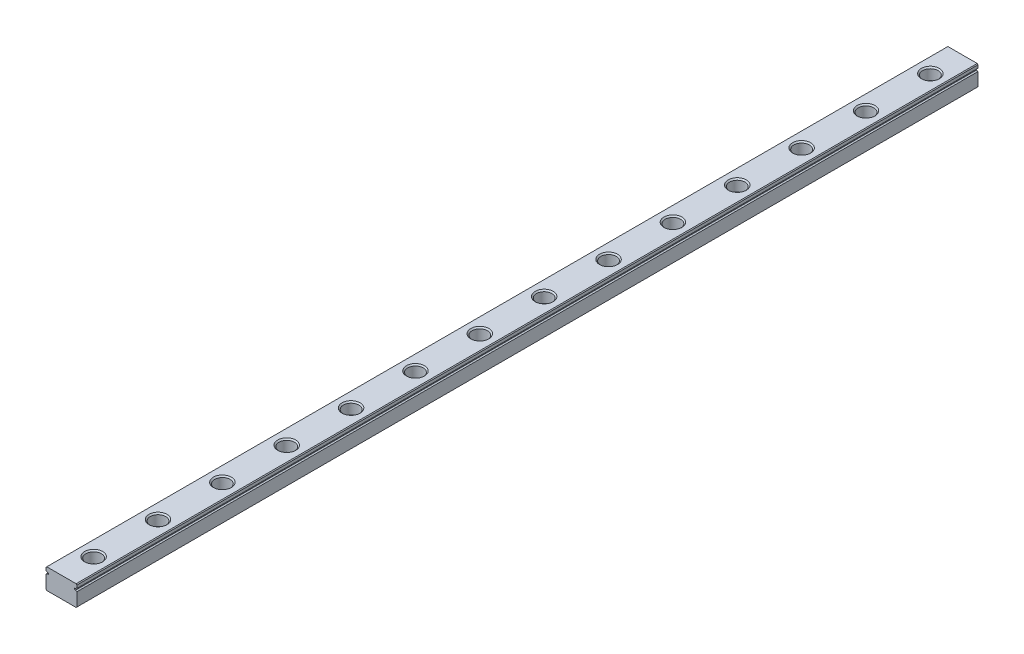
SolidWorks part; units mm, degrees
material "AISI 1045 鋼，冷拉"
ref_plane "Front Plane" through (0, 0, 0) normal (0, 0, 1) x (1, 0, 0)
ref_plane "Top Plane" through (0, 0, 0) normal (0, 1, 0) x (1, 0, 0)
ref_plane "Right Plane" through (0, 0, 0) normal (1, 0, 0) x (0, 0, -1)
sketch "Sketch1" plane through (0, 0, 0) normal (0, 0, 1) x (1, 0, 0)
  line L0 (-6, -4) -> (-6, 4) construction
  line L1 (-6, 4) -> (6, 4)
  line L2 (-6, -4) -> (6, -4)
  line L3 (-6, 4) -> (-6, 2.75)
  line L4 (-6, 2.75) -> (-5.5, 2.25) construction
  line L5 (-5.5, 2.25) -> (-5, 2.25)
  line L6 (-5.5, 1.75) -> (-6, 1.25) construction
  line L7 (-6, 1.25) -> (-6, -4)
  line L8 (-5, 2.25) -> (-5, 1.75)
  line L9 (-5, 1.75) -> (-5.5, 1.75)
  line L10 (-5.5, 1.75) -> (-5.25, 2) construction
  line L11 (-5.25, 2) -> (-5.5, 2.25) construction
  line L12 (-6, 2.75) -> (-6, 2.559)
  line L13 (-6, 1.25) -> (-6, 1.441)
  line L14 (0, 4) -> (0, -4) construction
  line L15 (5.25, 2) -> (5.5, 2.25) construction
  line L16 (5.5, 1.75) -> (5.25, 2) construction
  line L17 (5.5, 1.75) -> (6, 1.25) construction
  line L18 (6, 2.75) -> (5.5, 2.25) construction
  line L19 (6, -4) -> (6, 4) construction
  line L20 (6, 1.25) -> (6, 1.441)
  line L21 (6, 2.75) -> (6, 2.559)
  line L22 (5, 1.75) -> (5.5, 1.75)
  line L23 (5, 2.25) -> (5, 1.75)
  line L24 (6, 1.25) -> (6, -4)
  line L25 (5.5, 2.25) -> (5, 2.25)
  line L26 (6, 4) -> (6, 2.75)
  arc A0 (-6, 1.441) -> (-5.5, 1.75) centre (-6, 2) ccw
  arc A1 (-5.5, 2.25) -> (-6, 2.559) centre (-6, 2) ccw
  arc A2 (5.5, 2.25) -> (6, 2.559) centre (6, 2) cw
  arc A3 (6, 1.441) -> (5.5, 1.75) centre (6, 2) cw
  point P4 (-5, 2)
  point P28 (5, 2)
  dimension "D1" = 8
  dimension "D2" = 6
  dimension "D3" = 0.5
  dimension "D4" = 45
  dimension "D5" = 2
  dimension "D6" = 1
extrude "Boss-Extrude1" add sketch "Sketch1" along normal blind 350
chamfer "Chamfer1" distance 0.3 angle 45 4 edges at (-6, -4, 175) (6, -4, 175) (-6, 4, 175) (6, 4, 175)
hole_wizard "M3 六角承窩頭蓋螺釘的柱孔1" positions "3DSketch1" profile "Sketch3" counterbore size "M3" standard "ISO" end condition through all
sketch3d "3DSketch1"
  line L0 (0, 4, 0) -> (0, 4, 12.5) construction
  line L1 (5.7, 4, 0) -> (-5.7, 4, 0) construction
  point P0 (0, 4, 12.5)
  dimension "D1" = 12.5
sketch "Sketch3" plane through (0, 4, 12.5) normal (1, 0, 0) x (0, 0, 1)
  line L0 (0, 0) -> (0, 8)
  line L1 (1.75, 7.75) -> (2, 8)
  line L2 (3, 4.5) -> (1.75, 4.5)
  line L3 (1.75, 4.5) -> (1.75, 7.75)
  line L5 (3, 4.5) -> (3, 0.5)
  line L6 (3, 0.5) -> (3.5, 0)
  line L7 (3.5, 0) -> (0, 0)
  line L8 (-3, 0.5) -> (-3.5, 0) construction
  line L11 (0, -6.35) -> (0, 107.95) construction
  line L12 (2, 8) -> (0, 8)
  line L13 (-1.75, 7.75) -> (-2, 8) construction
  dimension "Thru Hole Dia." = 3.5
  dimension "Thru Hole Depth" = 8
  dimension "C'Bore Dia." = 6
  dimension "C'Bore Depth" = 4.5
  dimension "Near C'Sink Dia." = 7
  dimension "Near C'Sink Angle" = 90
  dimension "Far C'Sink Dia." = 4
  dimension "Far C'Sink Angle" = 90
pattern_linear "LPattern1" count 14 spacing 25 along (0, 0, 1) of "M3 六角承窩頭蓋螺釘的柱孔1"
